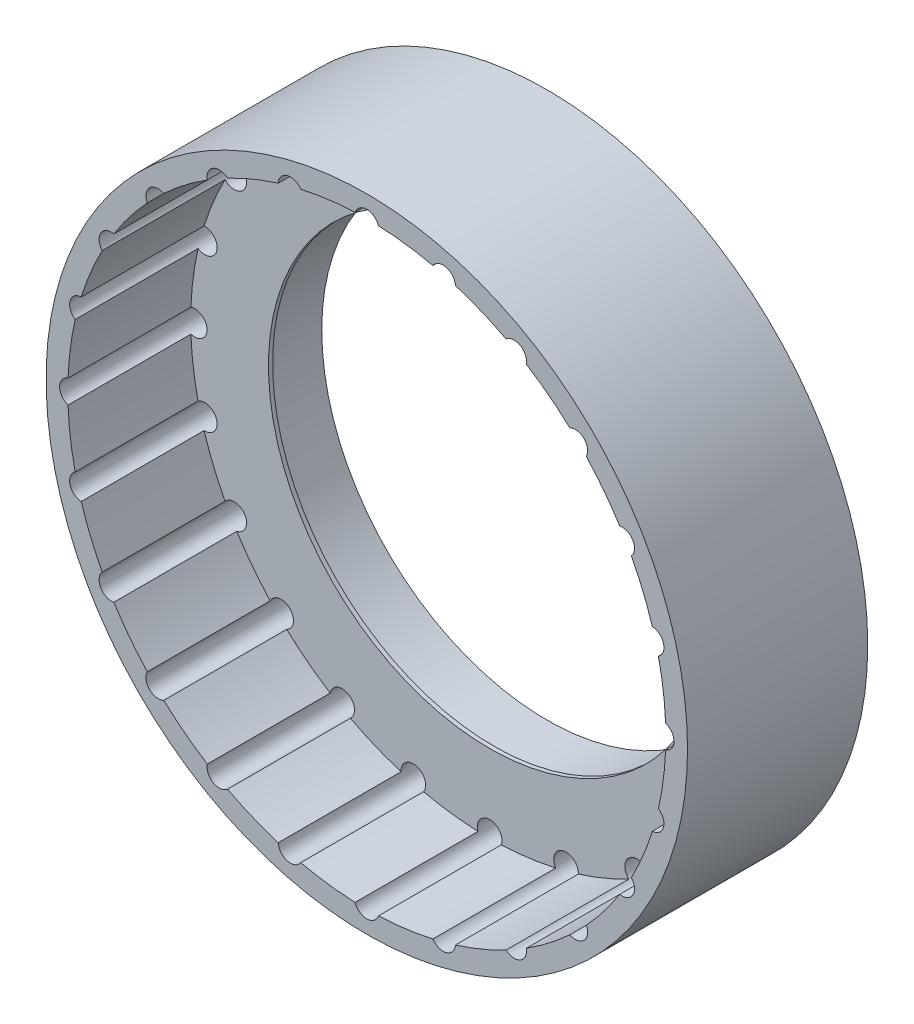
SolidWorks part; units mm, degrees
material "ABS"
ref_plane "Front Plane" through (0, 0, 0) normal (0, 0, 1) x (1, 0, 0)
ref_plane "Top Plane" through (0, 0, 0) normal (0, 1, 0) x (1, 0, 0)
ref_plane "Right Plane" through (0, 0, 0) normal (1, 0, 0) x (0, 0, -1)
sketch "CYC Master Sketch" plane through (0, 0, 0) normal (0, 0, 1) x (1, 0, 0)
  circle A0 centre (0, 0) radius 39.15
  circle A2 centre (0, 0) radius 36 construction
  circle A3 centre (-36, 0) radius 1.5
  circle A4 centre (-34.7733, 9.3175) radius 1.5
  circle A5 centre (-31.1769, 18) radius 1.5
  circle A6 centre (-25.4558, 25.4558) radius 1.5
  circle A7 centre (-18, 31.1769) radius 1.5
  circle A8 centre (-9.3175, 34.7733) radius 1.5
  circle A9 centre (0, 36) radius 1.5
  circle A10 centre (9.3175, 34.7733) radius 1.5
  circle A11 centre (18, 31.1769) radius 1.5
  circle A12 centre (25.4558, 25.4558) radius 1.5
  circle A13 centre (31.1769, 18) radius 1.5
  circle A14 centre (34.7733, 9.3175) radius 1.5
  circle A15 centre (36, 0) radius 1.5
  circle A16 centre (34.7733, -9.3175) radius 1.5
  circle A17 centre (31.1769, -18) radius 1.5
  circle A18 centre (25.4558, -25.4558) radius 1.5
  circle A19 centre (18, -31.1769) radius 1.5
  circle A20 centre (9.3175, -34.7733) radius 1.5
  circle A21 centre (0, -36) radius 1.5
  circle A22 centre (-9.3175, -34.7733) radius 1.5
  circle A23 centre (0, 0) radius 36.5
  circle A24 centre (-18, -31.1769) radius 1.5
  circle A25 centre (-25.4558, -25.4558) radius 1.5
  circle A26 centre (-31.1769, -18) radius 1.5
  circle A27 centre (-34.7733, -9.3175) radius 1.5
  point P6 (0, 0)
  point P47 (0, 0)
extrude "Gearbox Wall" add sketch "CYC Master Sketch" along normal blind 22 contours A0 A23 A13 A14 A15 A16 A17 A18 A19 A20 A21 A22 A3 A4 A5 A6 A7 A8 A9 A10 A11 A12 region at (-38.0427, 0, 0)
extrude "Gearbox Bottom" add sketch "CYC Master Sketch<3>" along normal blind 7 contours A21 A23 | A23 A20 | A20 A23 | A23 A19 | A19 A23 | A23 A18 | A18 A23 | A23 A17 | A17 A23 | A23 A16 | A16 A23 | A23 A15 | A15 A23 | A23 A14 | A14 A23 | A23 A13 | A13 A23 | A23 A12 | A12 A23 | A23 A11 | A11 A23 | A23 A10 | A10 A23 | A23 A9 | A9 A23 | A23 A8 | A8 A23 | A23 A7 | A7 A23 | A23 A6 | A6 A23 | A23 A5 | A5 A23 | A23 A4 | A4 A23 | A23 A3 | A3 A23 | A23 A22 | A22 A23 | A13 A23 A12 A11 A10 A9 A8 A7 A6 A5 A4 A3 A22 A21 A20 A19 A18 A17 A16 A15 A14 | A24 | A25 | A26 | A27 | A21 region at (-35.6188, 0, 0) region at (0, 0, 0) region at (-36.9089, 0, 0) region at (-34.4051, 9.2188, 0) region at (-35.6513, 9.5527, 0) region at (-30.8468, 17.8094, 0) region at (-31.9641, 18.4545, 0) region at (-25.1863, 25.1863, 0) region at (-26.0986, 26.0986, 0) region at (-17.8094, 30.8468, 0) region at (-18.4545, 31.9641, 0) region at (-9.2188, 34.4051, 0) region at (-9.5527, 35.6513, 0) region at (-9.5527, -35.6513, 0) region at (-9.2188, -34.4051, 0) region at (0, 35.6188, 0) region at (0, 36.9089, 0) region at (0, -35.6188, 0) region at (9.2188, 34.4051, 0) region at (9.5527, 35.6513, 0) region at (9.5527, -35.6513, 0) region at (9.2188, -34.4051, 0) region at (17.8094, 30.8468, 0) region at (18.4545, 31.9641, 0) region at (18.4545, -31.9641, 0) region at (17.8094, -30.8468, 0) region at (25.1863, 25.1863, 0) region at (26.0986, 26.0986, 0) region at (26.0986, -26.0986, 0) region at (25.1863, -25.1863, 0) region at (30.8468, 17.8094, 0) region at (31.9641, 18.4545, 0) region at (31.9641, -18.4545, 0) region at (30.8468, -17.8094, 0) region at (34.4051, 9.2188, 0) region at (35.6513, 9.5527, 0) region at (35.6513, -9.5527, 0) region at (34.4051, -9.2188, 0) region at (35.6188, 0, 0) region at (36.9089, 0, 0)
sketch "CYC Master Sketch<3>" plane through (0, 0, 0) normal (0, 0, 1) x (1, 0, 0) same geometry as "CYC Master Sketch"
extrude "Pin Cut" cut sketch "CYC Master Sketch<2>" against normal blind 3 from surface contours A23 A7 | A7 A23 | A23 A6 | A6 A23 | A23 A5 | A5 A23 | A23 A4 | A4 A23 | A23 A3 | A3 A23 | A23 A22 | A22 A23 | A23 A21 | A21 A23 | A23 A20 | A20 A23 | A23 A19 | A19 A23 | A23 A18 | A18 A23 | A23 A17 | A17 A23 | A16 A23 | A23 A16 | A15 A23 | A23 A15 | A23 A14 | A14 A23 | A23 A13 | A13 A23 | A23 A12 | A12 A23 | A23 A11 | A11 A23 | A10 A23 | A23 A9 | A9 A23 | A23 A8 | A8 A23 | A23 A10 | A23 A24 | A23 A24 | A23 A25 | A23 A25 | A23 A26 | A23 A26 | A23 A27 | A23 A27 region at (-35.6188, 0, 0) region at (-36.9089, 0, 0) region at (-34.4051, 9.2188, 0) region at (-35.6513, 9.5527, 0) region at (-34.4051, -9.2188, 0) region at (-35.6513, -9.5527, 0) region at (-30.8468, 17.8094, 0) region at (-31.9641, 18.4545, 0) region at (-30.8468, -17.8094, 0) region at (-31.9641, -18.4545, 0) region at (-25.1863, 25.1863, 0) region at (-26.0986, 26.0986, 0) region at (-25.1863, -25.1863, 0) region at (-26.0986, -26.0986, 0) region at (-17.8094, 30.8468, 0) region at (-18.4545, 31.9641, 0) region at (-17.8094, -30.8468, 0) region at (-18.4545, -31.9641, 0) region at (-9.2188, 34.4051, 0) region at (-9.5527, 35.6513, 0) region at (-9.5527, -35.6513, 0) region at (-9.2188, -34.4051, 0) region at (0, 35.6188, 0) region at (0, 36.9089, 0) region at (0, -36.9089, 0) region at (0, -35.6188, 0) region at (9.2188, 34.4051, 0) region at (9.5527, 35.6513, 0) region at (9.5527, -35.6513, 0) region at (9.2188, -34.4051, 0) region at (17.8094, 30.8468, 0) region at (18.4545, 31.9641, 0) region at (18.4545, -31.9641, 0) region at (17.8094, -30.8468, 0) region at (25.1863, 25.1863, 0) region at (26.0986, 26.0986, 0) region at (26.0986, -26.0986, 0) region at (25.1863, -25.1863, 0) region at (30.8468, 17.8094, 0) region at (31.9641, 18.4545, 0) region at (31.9641, -18.4545, 0) region at (30.8468, -17.8094, 0) region at (34.4051, 9.2188, 0) region at (35.6513, 9.5527, 0) region at (35.6513, -9.5527, 0) region at (34.4051, -9.2188, 0) region at (35.6188, 0, 0) region at (36.9089, 0, 0) starting at face at (0, 0, 7)
sketch "CYC Master Sketch<2>" plane through (0, 0, 0) normal (0, 0, 1) x (1, 0, 0) same geometry as "CYC Master Sketch"
sketch "Sketch3" plane through (0, 0, 7) normal (0, 0, 1) x (1, 0, 0)
  circle A0 centre (0, 0) radius 27.5
  dimension "D1" = 55
extrude "Bearing Cut" cut sketch "Sketch3" against normal through all from offset 0.5 offset against normal yes
sketch "Sketch4" plane through (0, 0, 6.5) normal (0, 0, 1) x (1, 0, 0)
  circle A0 centre (0, 0) radius 27
  dimension "D1" = 54
extrude "Bearing Retainer" cut sketch "Sketch4" along normal through all
